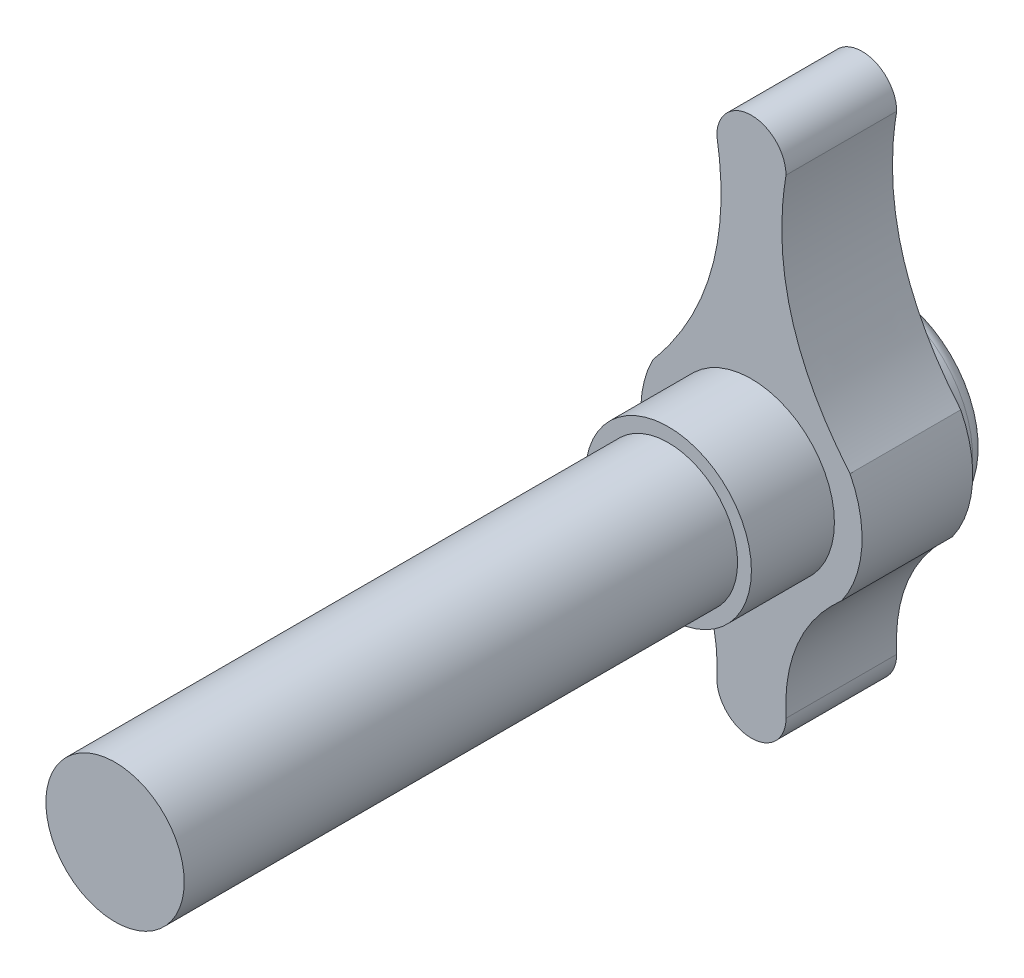
SolidWorks part; units mm, degrees
ref_plane "前视基准面" through (0, 0, 0) normal (0, 0, 1) x (1, 0, 0)
ref_plane "上视基准面" through (0, 0, 0) normal (0, 1, 0) x (1, 0, 0)
ref_plane "右视基准面" through (0, 0, 0) normal (1, 0, 0) x (0, 0, -1)
sketch "草图1" plane through (0, 0, 0) normal (0, 0, 1) x (1, 0, 0)
  arc A0 (3.2648, -2.3111) -> (3.5645, 1.815) centre (0, 0) ccw
  arc A1 (1.25, 10) -> (-1.25, 10) centre (0, 10) ccw
  arc A2 (-1.25, -7) -> (1.25, -7) centre (0, -7) ccw
  arc A3 (-3.5645, 1.815) -> (-3.2648, -2.3111) centre (0, 0) ccw
  spline S0 degree 2 poles (-3.2648, -2.3111) (-1.0958, -4.2281) (-1.25, -7) knots 0 0 0 1 1 1
  spline S1 degree 2 poles (3.2648, -2.3111) (1.0958, -4.2281) (1.25, -7) knots 0 0 0 1 1 1
  spline S2 degree 2 poles (-3.5645, 1.815) (-0.4838, 5.4605) (-1.25, 10) knots 0 0 0 1 1 1
  spline S3 degree 2 poles (3.5645, 1.815) (0.4838, 5.4605) (1.25, 10) knots 0 0 0 1 1 1
extrude "凸台-拉伸1" add sketch "草图1" along normal blind 4
sketch "草图2" plane through (0, 0, 0) normal (0, 0, -1) x (-1, 0, 0)
  circle A0 centre (0, 0.0982) radius 3.4897
extrude "凸台-拉伸2" add sketch "草图2" along normal blind 1
sketch "草图3" plane through (0, 0, -1) normal (0, 0, -1) x (-1, 0, 0)
  circle A0 centre (0, 0) radius 2.1511
extrude "切除-拉伸1" cut sketch "草图3" against normal blind 0.5
fillet "圆角1" radius 0.5 1 edges at (-2.1511, 0, -0.5)
fillet "圆角2" radius 0.5 1 edges at (-3.4897, 0.0982, -1)
sketch "草图4" plane through (0, 0, 4) normal (0, 0, 1) x (1, 0, 0)
  circle A0 centre (0, 0) radius 3
extrude "凸台-拉伸3" add sketch "草图4" along normal blind 3
sketch "草图5" plane through (0, 0, 7) normal (0, 0, 1) x (1, 0, 0)
  circle A0 centre (0, 0) radius 2.5
extrude "凸台-拉伸4" add sketch "草图5" along normal blind 20
